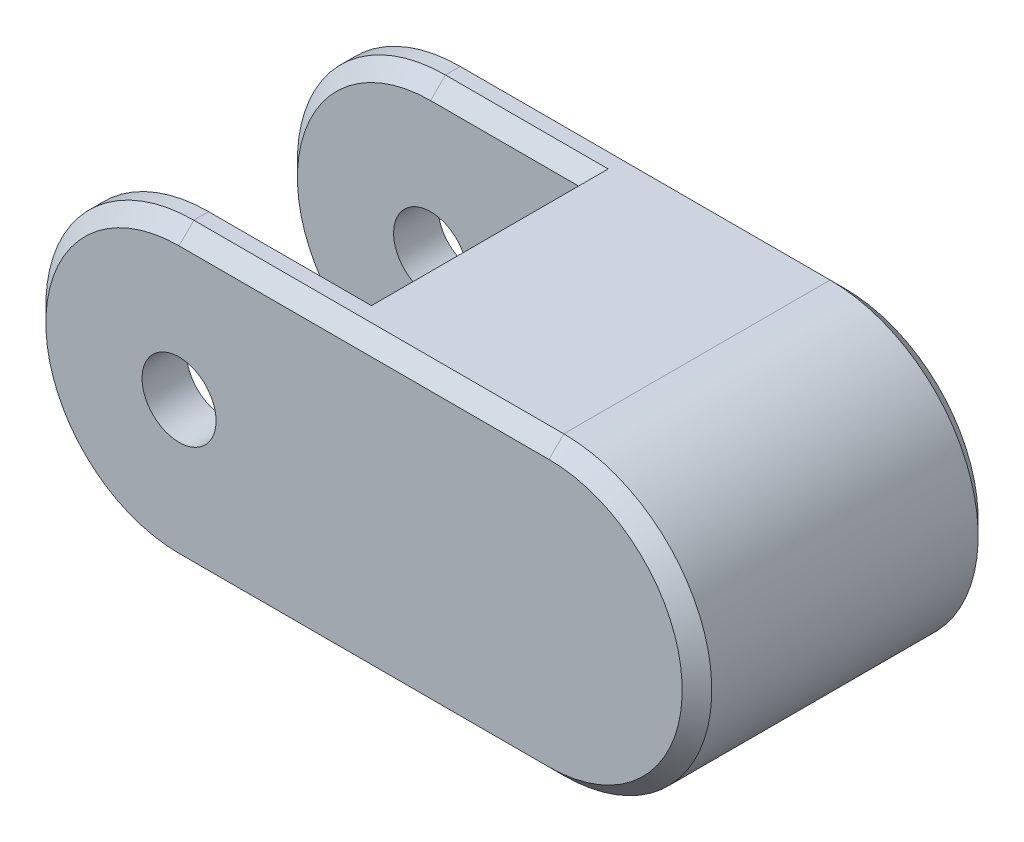
SolidWorks part; units mm, degrees
ref_plane "Front Plane" through (0, 0, 0) normal (0, 0, 1) x (1, 0, 0)
ref_plane "Top Plane" through (0, 0, 0) normal (0, 1, 0) x (1, 0, 0)
ref_plane "Right Plane" through (0, 0, 0) normal (1, 0, 0) x (0, 0, -1)
sketch "Sketch1" plane through (0, 0, 0) normal (0, 0, 1) x (1, 0, 0)
  line L0 (-12.5, 0) -> (12.5, 0) construction
  line L1 (-12.5, 10) -> (12.5, 10)
  line L2 (-12.5, -10) -> (12.5, -10)
  arc A0 (-12.5, 10) -> (-12.5, -10) centre (-12.5, 0) ccw
  arc A1 (12.5, -10) -> (12.5, 10) centre (12.5, 0) ccw
  point P3 (0, 0)
  dimension "D1" = 20
  dimension "D2" = 25
extrude "Boss-Extrude1" add sketch "Sketch1" along normal mid plane 20
sketch "Sketch2" plane through (0, 0, 0) normal (0, 0, 1) x (1, 0, 0)
  line L0 (-12.5, 10) -> (-2.5, 10)
  line L1 (-2.5, 10) -> (-2.5, -10)
  line L2 (-2.5, -10) -> (-12.5, -10)
  arc A0 (-12.5, 10) -> (-12.5, -10) centre (-12.5, 0) ccw
  dimension "D1" = 20
extrude "Cut-Extrude1" cut sketch "Sketch2" against normal mid plane 14
chamfer "Chamfer2" distance 1 angle 45 6 edges at (-7.5, -10, 7) (-22.5, 0, 7) (-7.5, 10, 7) (-7.5, -10, -7) (-22.5, 0, -7) (-7.5, 10, -7)
chamfer "Chamfer3" distance 1 angle 45 8 edges at (0, -10, 10) (22.5, 0, 10) (-22.5, 0, 10) (0, 10, 10) (0, -10, -10) (22.5, 0, -10) (-22.5, 0, -10) (0, 10, -10)
sketch "Sketch3" plane through (0, 0, 0) normal (0, 0, 1) x (1, 0, 0)
  circle A0 centre (-12.5, 0) radius 2.5
  dimension "D1" = 5
extrude "Cut-Extrude2" cut sketch "Sketch3" against normal mid plane 20
shell "Shell2" thickness 3 removed face at (-2.5, 0, 0)
chamfer "Chamfer4" distance 1 angle 45 2 edges at (-2.5, -10, 0) (-2.5, 10, 0)
